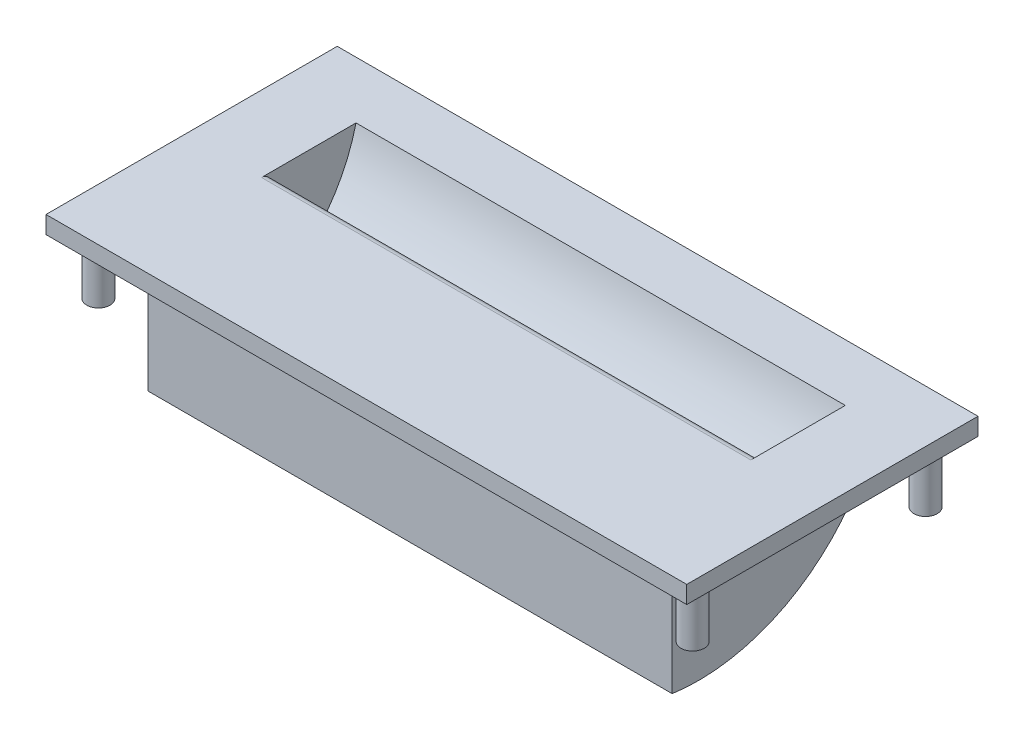
SolidWorks part; units mm, degrees
ref_plane "前视基准面" through (0, 0, 0) normal (0, 0, 1) x (1, 0, 0)
ref_plane "上视基准面" through (0, 0, 0) normal (0, 1, 0) x (1, 0, 0)
ref_plane "右视基准面" through (0, 0, 0) normal (1, 0, 0) x (0, 0, -1)
sketch "草图1" plane through (0, 0, 0) normal (0, 1, 0) x (1, 0, 0)
  line L1 (-55, -25) -> (55, -25)
  line L2 (-55, -25) -> (-55, 25)
  line L3 (-55, 25) -> (55, 25)
  line L4 (55, -25) -> (55, 25)
  line L5 (-55, -25) -> (55, 25) construction
  line L6 (-55, 25) -> (55, -25) construction
  point P0 (0, 0)
  dimension "D1" = 110
  dimension "D2" = 50
extrude "凸台-拉伸1" add sketch "草图1" along normal blind 3
sketch "草图2" plane through (0, 0, 0) normal (1, 0, 0) x (0, 0, -1)
  line L0 (-17.5, 0) -> (-17.5, -22)
  line L1 (-25, 0) -> (25, 0) construction
  line L2 (17.5, 0) -> (-17.5, 0)
  line L4 (0, -3.9011) -> (0, 6.3416) construction
  arc A0 (-17.5, -22) -> (17.5, 0) centre (-13.0001, 9.682) ccw
  dimension "D3" = 32
  dimension "D1" = 22
  dimension "D2" = 35
extrude "凸台-拉伸2" add sketch "草图2" along normal mid plane 90
sketch "草图6" plane through (0, 0, 0) normal (0, -1, 0) x (1, 0, 0)
  line L3 (-1000, 0) -> (49000, 0) construction
  line L4 (0, -1000) -> (0, 49000) construction
  circle A0 centre (-51, 20) radius 2
  circle A1 centre (-51, -20) radius 2
  circle A2 centre (51, 20) radius 2
  circle A3 centre (51, -20) radius 2
  dimension "D1" = 4
  dimension "D2" = 51
  dimension "D3" = 20
extrude "固定螺栓" add sketch "草图6" along normal blind 10
sketch "草图7" plane through (0, 0, 0) normal (1, 0, 0) x (0, 0, -1)
  line L4 (-25, 3) -> (25, 3) construction
  line L5 (-14.5, 0) -> (-14.5, -19.2792)
  line L6 (-14.5, 3) -> (-14.5, -19.2792)
  line L9 (15.2195, 3) -> (-14.5, 3)
  arc A5 (-14.5, -19.2792) -> (14.6406, 0.9077) centre (-13.0001, 9.682) ccw
  arc A6 (-14.5, -19.2792) -> (15.2195, 3) centre (-13.0001, 9.682) ccw
  dimension "D1" = 3
extrude "切除-拉伸1" cut sketch "草图7" against normal mid plane 84
sketch "草图8" plane through (0, 0, 14.5) normal (0, 0, -1) x (-1, 0, 0)
  line L0 (-42, 3) -> (42, 3)
  line L1 (42, 3) -> (42, 0)
  line L2 (42, 0) -> (-42, 0)
  line L3 (-42, 0) -> (-42, 3)
  dimension "D1" = 3
extrude "凸台-拉伸3" add sketch "草图8" along normal blind 15
fillet "圆角1" radius 1.5 2 edges at (0, 0, -0.5) (0, 3, -0.5)
